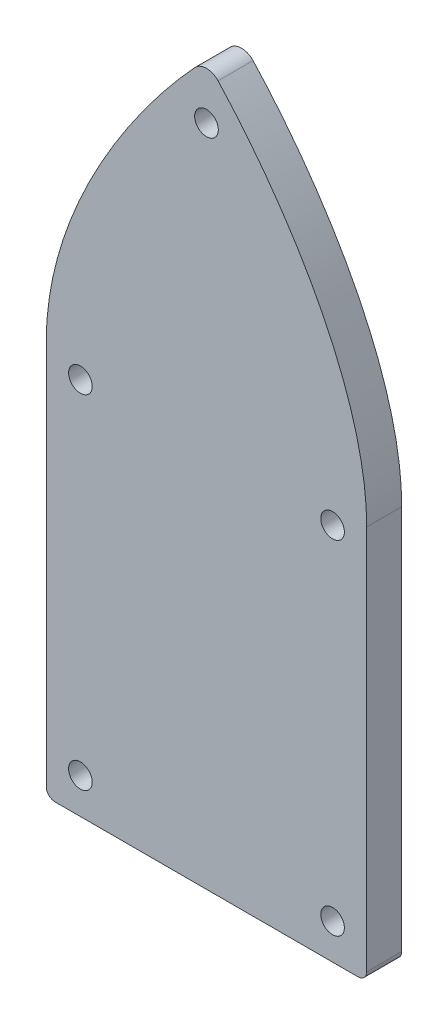
SolidWorks part; units mm, degrees
ref_plane "Front Plane" through (0, 0, 0) normal (0, 0, 1) x (1, 0, 0)
ref_plane "Top Plane" through (0, 0, 0) normal (0, 1, 0) x (1, 0, 0)
ref_plane "Right Plane" through (0, 0, 0) normal (1, 0, 0) x (0, 0, -1)
sketch "Sketch1" plane through (0, 0, 0) normal (0, 0, 1) x (1, 0, 0)
  line L0 (0, 72) -> (0, 0) construction
  line L1 (12, 0) -> (-12, 0)
  line L2 (-12, 0) -> (-12, 42)
  line L3 (-12, 42) -> (-11, 56)
  line L4 (-11, 56) -> (-7, 66)
  line L5 (-7, 66) -> (-1.7, 72)
  line L6 (-1.7, 72) -> (1.7, 72)
  line L7 (7, 66) -> (1.7, 72)
  line L8 (11, 56) -> (7, 66)
  line L9 (12, 42) -> (11, 56)
  line L10 (12, 0) -> (12, 42)
  dimension "D1" = 3.4
  dimension "D2" = 5.3
  dimension "D3" = 6
  dimension "D4" = 4
  dimension "D5" = 10
  dimension "D6" = 1
  dimension "D7" = 14
  dimension "D8" = 42
sketch "Sketch2" plane through (0, 0, 0) normal (0, 0, 1) x (1, 0, 0)
  line L0 (0, -1.2) -> (0, 80.8) construction
  line L1 (-18.3, -1.2) -> (18.3, -1.2)
  line L2 (18.3, -1.2) -> (18.3, 43.8)
  line L4 (12, 0) -> (-12, 0) construction
  line L5 (12, 0) -> (12, 42) construction
  line L6 (0, 80.8) -> (-4.6292, 85.4292) construction
  line L7 (0, 80.8) -> (-5.4755, 80.8) construction
  line L8 (-18.3, -1.2) -> (-18.3, 43.8)
  spline S0 degree 3 poles (18.3, 43.8) (18.3, 58.8) (6.364, 74.436) (0, 80.8) knots 0 0 0 0 1 1 1 1
  spline S1 degree 3 poles (-18.3, 43.8) (-18.3, 58.8) (-6.364, 74.436) (0, 80.8) knots 0 0 0 0 1 1 1 1
  dimension "D6" = 45
  dimension "D7" = 27
  dimension "D1" = 82
  dimension "D2" = 1.2
  dimension "D3" = 6.3
  dimension "D4" = 45
  dimension "D5" = 45
extrude "Boss-Extrude1" add sketch "Sketch2" along normal blind 4
hole_wizard "CBORE for M5 Hex Head Bolt1" positions "Sketch3" profile "Sketch4" counterbore size "M5" standard "DIN" end condition through all
sketch "Sketch3" plane through (0, 0, 0) normal (0, 0, -1) x (-1, 0, 0)
  point P0 (14.4, 42.0178)
  point P3 (14.4, 2.8635)
  point P6 (-14.4, 2.8635)
  point P9 (-14.4, 42.0178)
  point P12 (0, 74.6)
sketch "Sketch4" plane through (-14.4, 42.0178, 0) normal (1, 0, 0) x (0, 1, 0)
  line L0 (0, 0) -> (0, 4)
  line L1 (0, 4) -> (1.35, 4)
  line L3 (1.35, 4) -> (1.35, 2)
  line L4 (1.35, 2) -> (2.5, 2)
  line L5 (2.5, 2) -> (2.5, 0)
  line L7 (2.5, 0) -> (0, 0)
  line L11 (0, -6.35) -> (0, 107.95) construction
  dimension "Thru Hole Dia." = 2.7
  dimension "Thru Hole Depth" = 4
  dimension "C'Bore Dia." = 5
  dimension "C'Bore Depth" = 2
ref_plane "Plane1" through (7, 0, 0) normal (1, 0, 0) x (0, 0, -1)
sketch "Sketch6" plane through (7, 0, 0) normal (1, 0, 0) x (0, 0, -1)
  line L0 (0, 44.8) -> (5.5, 44.8)
  line L1 (0, -1.2) -> (0, 43.8) construction
  line L2 (5.5, 34.8) -> (0, 34.8)
  line L3 (0, 34.8) -> (0, 44.8)
  line L4 (5.5, 34.8) -> (5.5, 44.8) construction
  line L6 (-4, 43.8) -> (0, 43.8) construction
  arc A0 (5.5, 44.8) -> (5.5, 34.8) centre (5.5, 39.8) cw
  circle A1 centre (5.5, 39.8) radius 1.75
  dimension "D1" = 3.5
  dimension "D2" = 5
  dimension "D3" = 5.5
  dimension "D4" = 1
extrude "Boss-Extrude2" add sketch "Sketch6" against normal blind 4
fillet "Fillet1" radius 5.5 2 edges at (5, 34.8, 0) (5, 44.8, 0)
mirror "Mirror1" about plane through (0, 0, 0) normal (1, 0, 0) of "Fillet1", "Boss-Extrude2"
sketch "Sketch9" plane through (0, 0, 0) normal (1, 0, 0) x (0, 0, -1)
  line L0 (27, 29.3) -> (27, -1.2) construction
  line L1 (0, -1.2) -> (0, 43.8) construction
  line L2 (27, -1.2) -> (0, -1.2) construction
  line L3 (27, 29.3) -> (0, 29.3) construction
  dimension "D1" = 27
fillet "Fillet2" radius 1.8 1 edges at (0, 80.8, 2)
fillet "Fillet3" radius 1 2 edges at (18.3, -1.2, 2) (-18.3, -1.2, 2)
